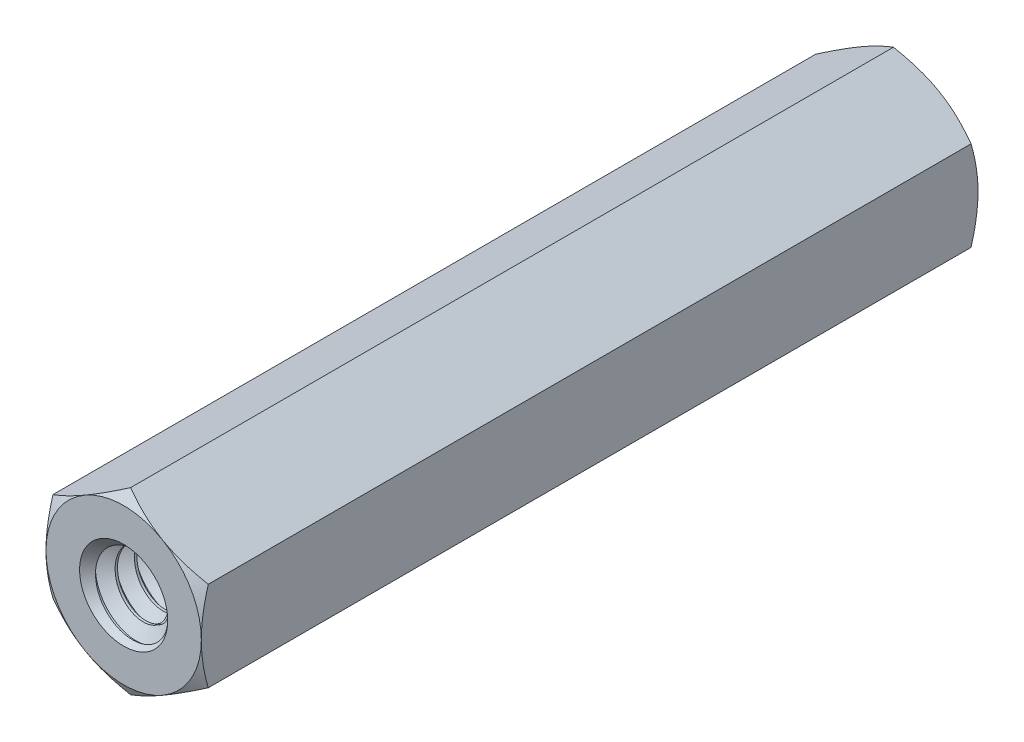
SolidWorks part; units mm, degrees
ref_plane "Front Plane" through (0, 0, 0) normal (0, 0, 1) x (1, 0, 0)
ref_plane "Top Plane" through (0, 0, 0) normal (0, 1, 0) x (1, 0, 0)
ref_plane "Right Plane" through (0, 0, 0) normal (1, 0, 0) x (0, 0, -1)
sketch "Sketch3" plane through (0, 0, 0) normal (1, 0, 0) x (0, 0, -1)
  line L0 (-15.875, 0) -> (15.875, 0) construction
  line L1 (0, 3.175) -> (0, -3.175) construction
  line L2 (-15.875, 1.7526) -> (-15.875, -1.7526) construction
  point P2 (6.35, 0)
  point P3 (-6.35, 0)
  dimension "Length" = 31.75
  dimension "Min Thread Length" = 9.525
  dimension "D1" = 9.525
  dimension "Thread Dia" = 3.5052
  dimension "Hex" = 6.35
sketch "Sketch1" plane through (0, 0, 0) normal (0, 0, 1) x (1, 0, 0)
  line L1 (0, 3.6662) -> (-3.175, 1.8331)
  line L2 (-3.175, 1.8331) -> (-3.175, -1.8331)
  line L3 (-3.175, -1.8331) -> (0, -3.6662)
  line L4 (0, -3.6662) -> (3.175, -1.8331)
  line L5 (3.175, -1.8331) -> (3.175, 1.8331)
  line L6 (3.175, 1.8331) -> (0, 3.6662)
  circle A0 centre (0, 0) radius 3.175 construction
  circle A1 centre (0, 0) radius 1.7526
extrude "Extrude1" add sketch "Sketch1" along normal up to vertex (15.875 mm away) and the other way up to vertex (15.875 mm away) up to point (0, 0, 15.875) other way up to point (0, 0, -15.875)
sketch "Sketch11" plane through (0, 0, -15.875) normal (0, 0, -1) x (-1, 0, 0)
  circle A0 centre (0, 0) radius 1.7526 construction
  circle A1 centre (0, 0) radius 1.7526
curve "Helix/Spiral1" pitch 0.7937 height 32.5437 radius 1.7526 centre (0, 0, -15.875) axis (0, 0, 1) start towards (0, 1, 0) parameters "Pitch"=0.7937
sketch "Sketch12" plane through (0, 0, 0) normal (1, 0, 0) x (0, 0, -1)
  line L0 (16.5695, 1.7526) -> (15.875, 1.7526)
  line L1 (16.5695, 1.7526) -> (16.2719, 1.237)
  line L2 (16.2719, 1.237) -> (16.1727, 1.237)
  line L3 (16.1727, 1.237) -> (15.875, 1.7526)
  line L4 (16.2223, 1.237) -> (16.2223, 1.7526) construction
  line L5 (16.4207, 1.4948) -> (16.0238, 1.4948) construction
  dimension "D1" = 0.0992
  dimension "D2" = 0.3969
  dimension "D3" = 60
sweep "Sweep1" add profiles "Sketch12" path "Helix/Spiral1"
sketch "Sketch6" plane through (0, 0, -15.875) normal (0, 0, -1) x (-1, 0, 0)
  line L6 (0, 3.6662) -> (-3.175, 1.8331)
  line L7 (-3.175, 1.8331) -> (-3.175, -1.8331)
  line L8 (-3.175, -1.8331) -> (0, -3.6662)
  line L9 (0, -3.6662) -> (3.175, -1.8331)
  line L10 (3.175, -1.8331) -> (3.175, 1.8331)
  line L11 (3.175, 1.8331) -> (0, 3.6662)
  line L12 (0, 3.6662) -> (-3.175, 1.8331)
  line L13 (-3.175, 1.8331) -> (-3.175, -1.8331)
  line L14 (-3.175, -1.8331) -> (0, -3.6662)
  line L15 (0, -3.6662) -> (3.175, -1.8331)
  line L16 (3.175, -1.8331) -> (3.175, 1.8331)
  line L17 (3.175, 1.8331) -> (0, 3.6662)
  dimension "D1" = 0
extrude "Extrude2" cut sketch "Sketch6" along normal through all
sketch "Sketch7" plane through (0, 0, -15.875) normal (0, 0, -1) x (-1, 0, 0)
  circle A2 centre (0, 0) radius 1.8034
  circle A3 centre (0, 0) radius 1.8034
  dimension "D1" = 0.0508
extrude "Extrude3" cut sketch "Sketch7" against normal through all draft 43
sketch "Sketch8" plane through (0, 0, -15.875) normal (0, 0, -1) x (-1, 0, 0)
  circle A0 centre (0, 0) radius 3.175 construction
  circle A1 centre (0, 0) radius 3.175
extrude "Extrude4" cut sketch "Sketch8" against normal through all draft 60 flip side to cut
mirror "Mirror1" about plane through (0, 0, 0) normal (0, 0, 1) of "Extrude2", "Extrude3", "Extrude4"
sketch "Sketch9" plane through (0, 0, 0) normal (1, 0, 0) x (0, 0, -1)
  line L1 (-6.35, 1.8034) -> (6.35, 1.8034)
  line L2 (-6.35, 1.8034) -> (-6.35, 0)
  line L3 (-6.35, 0) -> (6.35, 0)
  line L4 (6.35, 1.8034) -> (6.35, 0)
  line L7 (-15.875, 0) -> (15.875, 0) construction
revolve "Revolve" add sketch "Sketch9" angle 360 about L0
sketch "Sketch10" plane through (0, 0, 0) normal (1, 0, 0) x (0, 0, -1)
  line L0 (15.875, 1.7526) -> (6.35, 1.7526)
  line L1 (-15.875, 1.7526) -> (-6.35, 1.7526)
  line L2 (6.35, 1.7526) -> (6.35, -1.7526)
  line L3 (-15.875, -1.8034) -> (-6.35, -1.8034)
  line L4 (-6.35, 1.7526) -> (-6.35, -1.8034)
  line L5 (6.35, -1.7526) -> (15.875, -1.7526)
equation "\"D1@Sketch3\" = \"Min Thread Length@Sketch3\""
equation "\"D3@Helix/Spiral1\" = \"Length@Sketch3\"+\"Pitch@Helix/Spiral1\""
equation "\"D1@Sketch12\" = \"Pitch@Helix/Spiral1\"*.125"
equation "\"D2@Sketch12\" = \"Pitch@Helix/Spiral1\"*.5"
